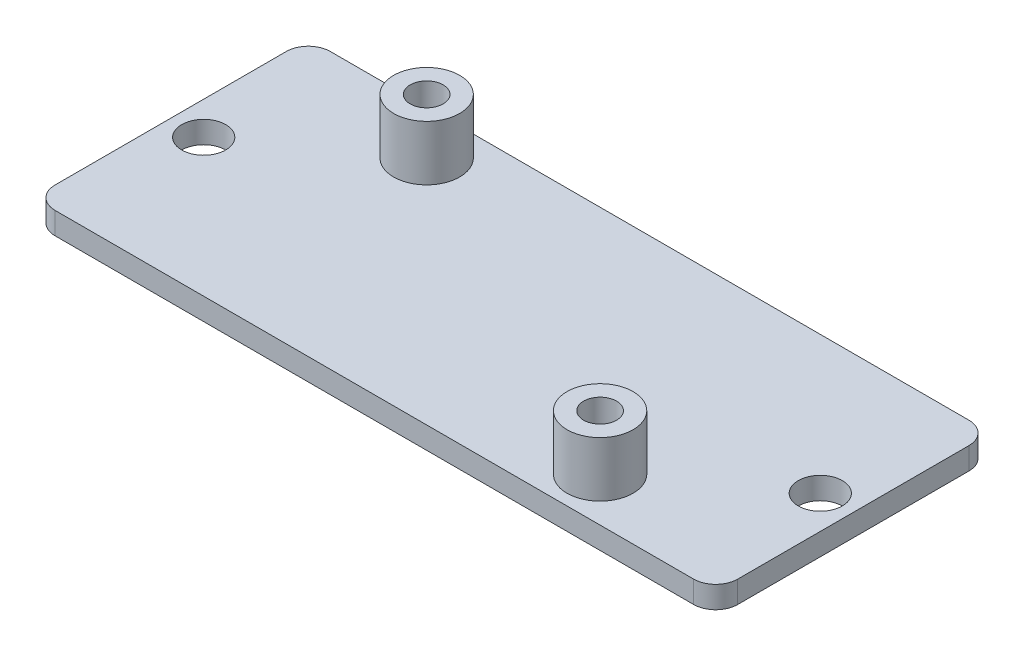
SolidWorks part; units mm, degrees
material "ABS"
ref_plane "Спереди" through (0, 0, 0) normal (0, 0, 1) x (1, 0, 0)
ref_plane "Сверху" through (0, 0, 0) normal (0, 1, 0) x (1, 0, 0)
ref_plane "Справа" through (0, 0, 0) normal (1, 0, 0) x (0, 0, -1)
sketch "Эскиз1" plane through (0, 0, 0) normal (0, 1, 0) x (1, 0, 0)
  line L1 (0, 0) -> (62, 0)
  line L2 (0, 0) -> (0, -25)
  line L3 (0, -25) -> (62, -25)
  line L4 (62, 0) -> (62, -25)
  dimension "D1" = 25
  dimension "D2" = 62
extrude "Бобышка-Вытянуть1" add sketch "Эскиз1" along normal blind 2
sketch "Эскиз2" plane through (0, 2, 0) normal (0, 1, 0) x (1, 0, 0)
  line L0 (0, 0) -> (0, -25) construction
  line L1 (62, -25) -> (62, 0) construction
  line L2 (62, 0) -> (0, 0) construction
  line L3 (0, -25) -> (62, -25) construction
  circle A0 centre (14.75, -4) radius 3
  circle A1 centre (47.5, -21) radius 3
  dimension "D2" = 14.5
  dimension "D4" = 4
  dimension "D5" = 6
  dimension "D6" = 6
  dimension "D1" = 14.75
  dimension "D3" = 4
extrude "Бобышка-Вытянуть2" add sketch "Эскиз2" along normal blind 5
sketch "Эскиз3" plane through (0, 7, 0) normal (0, 1, 0) x (1, 0, 0)
  circle A0 centre (14.75, -4) radius 1.5
  circle A1 centre (47.5, -21) radius 1.5
  dimension "D1" = 3
  dimension "D2" = 3
extrude "Вырез-Вытянуть1" cut sketch "Эскиз3" against normal through all both and the other way through all
sketch "Эскиз4" plane through (0, 2, 0) normal (0, 1, 0) x (1, 0, 0)
  line L0 (0, -12.5) -> (62, -12.5) construction
  line L1 (0, 0) -> (0, -25) construction
  line L2 (62, -25) -> (62, 0) construction
  circle A0 centre (3, -12.5) radius 2
  circle A1 centre (59, -12.5) radius 2
  dimension "D1" = 4
  dimension "D2" = 4
  dimension "D3" = 3
  dimension "D4" = 3
extrude "Вырез-Вытянуть2" cut sketch "Эскиз4" against normal through all both and the other way through all
fillet "Скругление1" radius 2 1 edges at (0, 1, 0) type face fillet first side face at (31, 1, 0) second side face at (0, 1, 12.5)
fillet "Скругление2" radius 2 1 edges at (0, 1, 25) type face fillet first side face at (0, 1, 13.5) second side face at (31, 1, 25)
fillet "Скругление3" radius 2 1 edges at (62, 1, 25) type face fillet first side face at (32, 1, 25) second side face at (62, 1, 12.5)
fillet "Скругление4" radius 2 1 edges at (62, 1, 0) type face fillet first side face at (62, 1, 11.5) second side face at (32, 1, 0)
